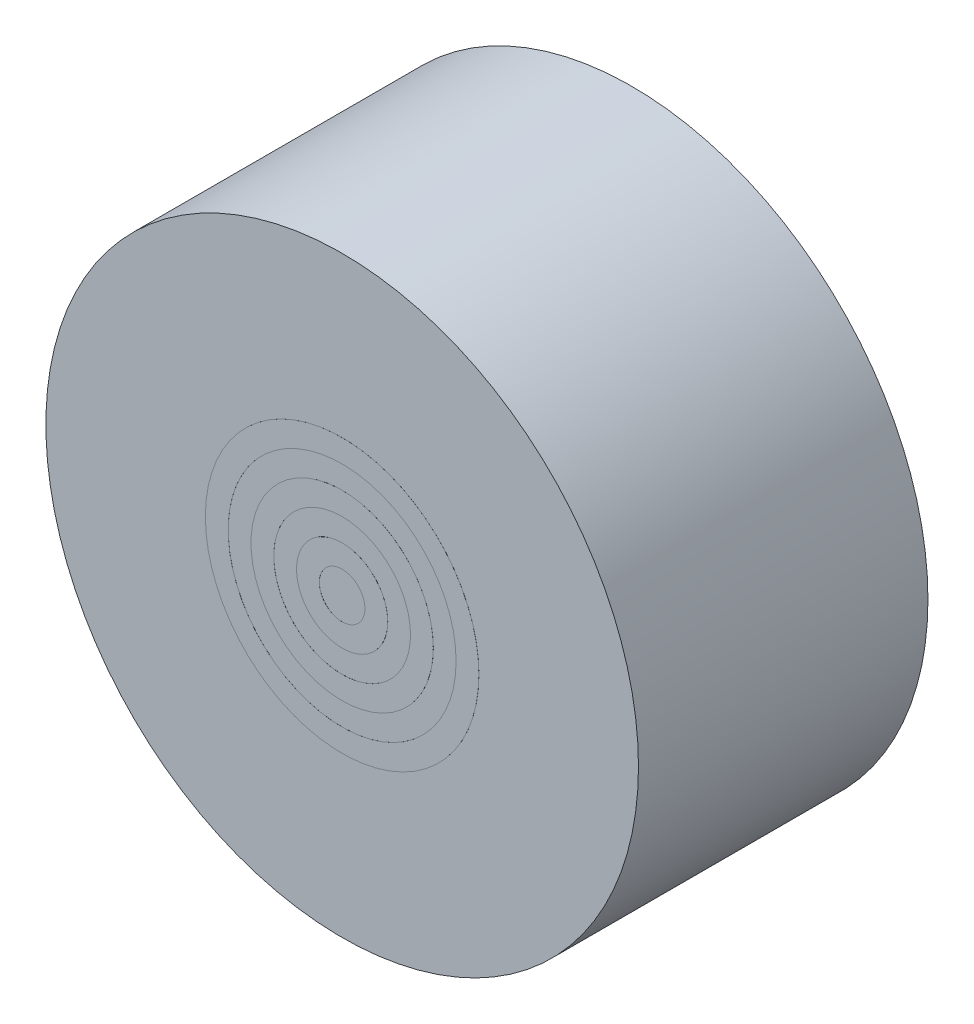
SolidWorks part; units mm, degrees
material "ULE_lidan (1)"
ref_plane "Front Plane" through (0, 0, 0) normal (0, 0, 1) x (1, 0, 0)
ref_plane "Top Plane" through (0, 0, 0) normal (0, 1, 0) x (1, 0, 0)
ref_plane "Right Plane" through (0, 0, 0) normal (1, 0, 0) x (0, 0, -1)
sketch "Sketch2" plane through (0, 0, 0) normal (0, 0, 1) x (1, 0, 0)
  line L0 (0, 0.5) -> (0, -0.5) construction
  circle A0 centre (0, 0) radius 0.5
extrude "0to0.5" add sketch "Sketch2" along normal blind 6.349
sketch "Sketch3" plane through (0, 0, 0) normal (0, 0, 1) x (1, 0, 0)
  circle A0 centre (0, 0) radius 0.5
  circle A1 centre (0, 0) radius 1
  dimension "D2" = 2
extrude "0.5to1" add sketch "Sketch3" along normal blind 6.351
sketch "Sketch4" plane through (0, 0, 0) normal (0, 0, 1) x (1, 0, 0)
  circle A0 centre (0, 0) radius 1
  circle A1 centre (0, 0) radius 1.5
  dimension "D1" = 2
  dimension "D2" = 3
extrude "1to1.5" add sketch "Sketch4" along normal blind 6.349
sketch "Sketch5" plane through (0, 0, 0) normal (0, 0, 1) x (1, 0, 0)
  circle A0 centre (0, 0) radius 1.5
  circle A1 centre (0, 0) radius 2
  dimension "D1" = 3
  dimension "D2" = 4
extrude "1.5to2" add sketch "Sketch5" along normal blind 6.351
sketch "Sketch6" plane through (0, 0, 0) normal (0, 0, 1) x (1, 0, 0)
  circle A0 centre (0, 0) radius 2
  circle A1 centre (0, 0) radius 2.5
  dimension "D1" = 4
  dimension "D2" = 5
extrude "2to2.5" add sketch "Sketch6" along normal blind 6.349
sketch "Sketch7" plane through (0, 0, 0) normal (0, 0, 1) x (1, 0, 0)
  circle A0 centre (0, 0) radius 2.5
  circle A1 centre (0, 0) radius 3
  dimension "D1" = 5
  dimension "D2" = 6
extrude "2.5to3" add sketch "Sketch7" along normal blind 6.351
sketch "Sketch8" plane through (0, 0, 0) normal (0, 0, 1) x (1, 0, 0)
  circle A0 centre (0, 0) radius 6.5
  dimension "D1" = 13
extrude "Mirror" add sketch "Sketch8" along normal blind 6.35
ref_axis "Axis1" through (0, 0, 6.35) along (0, 0, -1)
equation "\"Mult_size\"= 1"
equation "\"Mult2\"= 2"
equation "\"mult3\"= 3"
equation "\"DDD\"= 25.4 / 2"
equation "\"ttt\"= 25.4 / 4"
equation "\"D1@Sketch2\"= \"Mult_size\""
equation "\"D1@Sketch3\"= \"Mult_size\""
equation "\"D2@Sketch3\"= 2 * \"Mult_size\""
equation "\"D1@Sketch4\"= 2 * \"Mult_size\""
equation "\"D2@Sketch4\"= 3 *\"Mult_size\""
equation "\"D1@Sketch5\"= 3 * \"Mult_size\""
equation "\"D2@Sketch5\"= 4 * \"Mult_size\""
equation "\"D1@Sketch6\"= 4 * \"Mult_size\""
equation "\"D2@Sketch6\"= 5 * \"Mult_size\""
equation "\"D1@Sketch7\"= 5 * \"Mult_size\""
equation "\"D2@Sketch7\"= 6 * \"Mult_size\""
equation "\"D1@Sketch8\"= 13 * \"Mult_size\""
